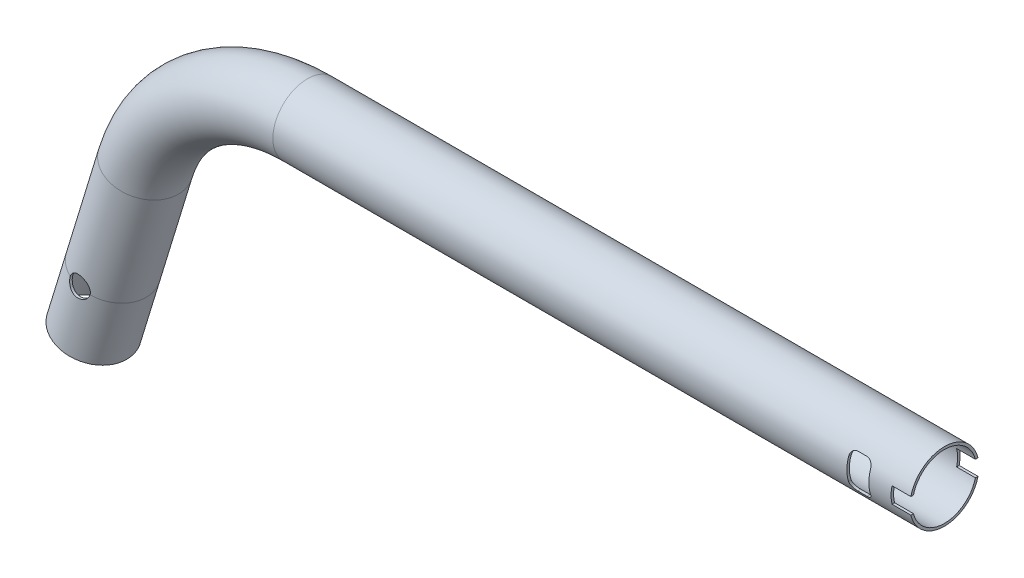
SolidWorks part; units mm, degrees
ref_plane "Front Plane" through (0, 0, 0) normal (0, 0, 1) x (1, 0, 0)
ref_plane "Top Plane" through (0, 0, 0) normal (0, 1, 0) x (1, 0, 0)
ref_plane "Right Plane" through (0, 0, 0) normal (1, 0, 0) x (0, 0, -1)
sketch "Sketch1" plane through (0, 0, 0) normal (0, 0, 1) x (1, 0, 0)
  line L0 (-93.1953, 0) -> (93.1953, 0)
  line L1 (-144.8358, -38.2119) -> (-155.1047, -71.8)
  line L2 (93.1953, 0) -> (109.7953, 0)
  line L3 (-155.1047, -71.8) -> (-161.2804, -92)
  arc A0 (-93.1953, 0) -> (-144.8358, -38.2119) centre (-93.1953, -54) ccw
  point P4 (0, 0)
  point P10 (-155.1047, -71.8)
  dimension "D2" = 54
  dimension "D1" = 73
  dimension "D3" = 71.8
  dimension "D4" = 248.3
  dimension "D5" = 92
  dimension "D6" = 73
  dimension "D7" = 16.6
ref_plane "Plane1" through (93.1953, 0, 0) normal (1, 0, 0) x (0, 0, -1)
sketch "Sketch3" plane through (93.1953, 0, 0) normal (1, 0, 0) x (0, 0, -1)
  circle A0 centre (0, 0) radius 11
  circle A1 centre (0, 0) radius 10.2
  dimension "D1" = 0.8
sweep "Sweep2" add profiles "Sketch3" path "Sketch1"
ref_axis "Axis1" through (109.7953, 0, 0) along (-1, 0, 0)
ref_axis "Axis2" through (-143.0374, -32.3296, 0) along (-0.2924, -0.9563, 0)
sketch "Sketch4" plane through (0, 0, 0) normal (0, 0, 1) x (1, 0, 0)
  line L0 (-165.624, -68.5839) -> (-144.5853, -75.0161) construction
  line L1 (93.1953, -101.4635) -> (93.1953, 101.4635) construction
  line L2 (109.7953, 0) -> (93.1953, 0) construction
  line L3 (109.7953, -11) -> (109.7953, 11) construction
  line L4 (109.7953, 0) -> (-93.1953, 0) construction
  line L11 (91.6953, -5.5) -> (94.6953, -5.5)
  line L16 (89.6953, -3.5) -> (89.6953, 3.5)
  line L17 (91.6953, 5.5) -> (94.6953, 5.5)
  line L22 (109.7953, 2.5555) -> (109.7953, -2.5555)
  line L23 (109.7953, -2.5555) -> (103.7896, -2.5555)
  line L24 (103.7896, -2.5555) -> (103.7896, 2.5555)
  line L25 (103.7896, 2.5555) -> (109.7953, 2.5555)
  line L26 (96.6953, -3.5) -> (96.6953, 3.5)
  line L27 (89.6953, -5.5) -> (96.6953, 5.5) construction
  line L28 (89.6953, 5.5) -> (96.6953, -5.5) construction
  circle A0 centre (-155.1047, -71.8) radius 3.3
  arc A6 (89.6953, -3.5) -> (91.6953, -5.5) centre (91.6953, -3.5) ccw
  arc A7 (94.6953, -5.5) -> (96.6953, -3.5) centre (94.6953, -3.5) ccw
  arc A8 (94.6953, 5.5) -> (96.6953, 3.5) centre (94.6953, 3.5) cw
  arc A9 (91.6953, 5.5) -> (89.6953, 3.5) centre (91.6953, 3.5) ccw
  dimension "D1" = 16.6
  dimension "D4" = 2
  dimension "D2" = 7
  dimension "D3" = 11
extrude "Cut-Extrude1" cut sketch "Sketch4" along normal up to next
sketch "Sketch5" plane through (0, 0, 0) normal (0, 0, 1) x (1, 0, 0)
  line L0 (-164.859, -68.8178) -> (-145.3504, -74.7822) construction
  circle A0 centre (-155.1047, -71.8) radius 3.3
extrude "Cut-Extrude2" cut sketch "Sketch5" against normal through all
sketch "Sketch6" plane through (0, 0, 0) normal (0, 0, 1) x (1, 0, 0)
  line L0 (109.7953, 2.5555) -> (103.7896, 2.5555)
  line L1 (103.7896, 2.5555) -> (103.7896, -2.5555)
  line L2 (103.7896, -2.5555) -> (109.7953, -2.5555)
  line L3 (109.7953, -2.5555) -> (109.7953, 2.5555)
extrude "Cut-Extrude3" cut sketch "Sketch6" against normal through all
